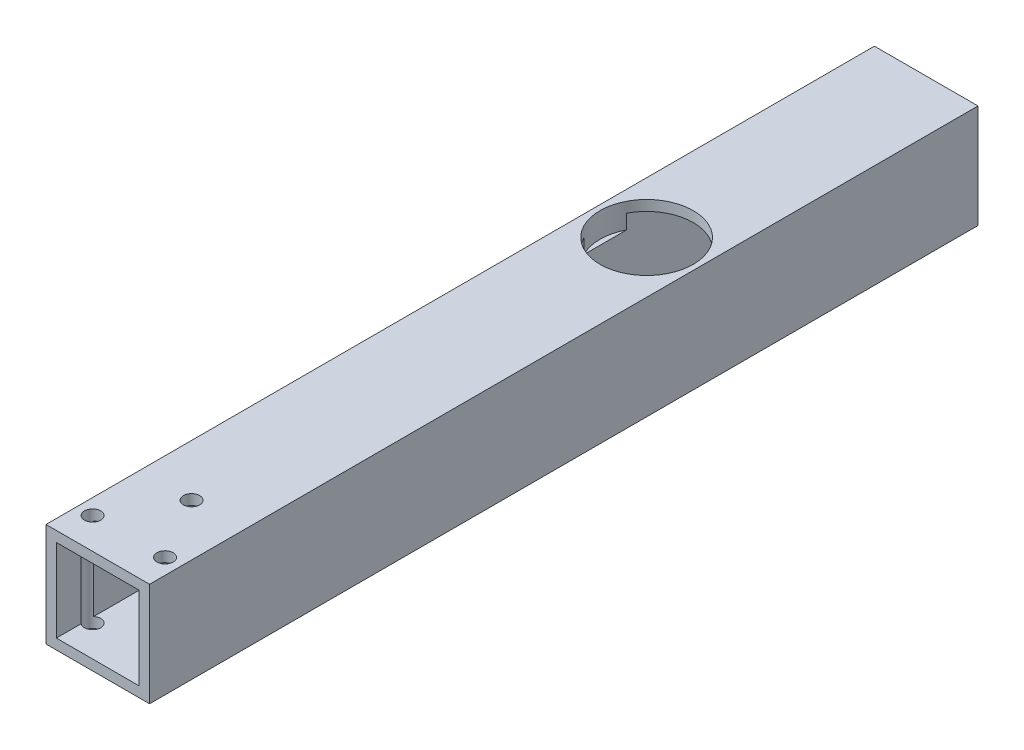
SolidWorks part; units mm, degrees
ref_plane "Front Plane" through (0, 0, 0) normal (0, 0, 1) x (1, 0, 0)
ref_plane "Top Plane" through (0, 0, 0) normal (0, 1, 0) x (1, 0, 0)
ref_plane "Right Plane" through (0, 0, 0) normal (1, 0, 0) x (0, 0, -1)
sketch "Sketch1" plane through (0, 0, 0) normal (0, 0, 1) x (1, 0, 0)
  line L0 (-12.7, 12.7) -> (12.7, 12.7)
  line L2 (-15.875, 15.875) -> (15.875, 15.875)
  line L3 (-15.875, 15.875) -> (-15.875, -15.875)
  line L4 (-15.875, -15.875) -> (15.875, -15.875)
  line L5 (15.875, 15.875) -> (15.875, -15.875)
  line L10 (12.7, 12.7) -> (12.7, -12.7)
  line L11 (-12.7, -12.7) -> (12.7, -12.7)
  line L12 (-12.7, 12.7) -> (-12.7, -12.7)
  point P12 (0, 15.875)
  point P14 (15.875, 0)
  dimension "Wall Thickness" = 3.175
  dimension "Outside Width" = 31.75
  dimension "Outside Height" = 31.75
  dimension "Inside Height" = 25.4
  dimension "Inside Width" = 25.4
sketch "Sketch2" plane through (0, 0, 0) normal (1, 0, 0) x (0, 0, -1)
  line L0 (127, 0) -> (-127, 0)
  point P4 (0, 0)
  point P7 (-127, 0)
  point P10 (127, 0)
  dimension "Length" = 254
sketch "Sketch3" plane through (0, 0, 0) normal (0, 0, 1) x (1, 0, 0)
  line L21 (15.875, 15.875) -> (-15.875, 15.875)
  line L22 (15.875, -15.875) -> (15.875, 15.875)
  line L23 (-15.875, -15.875) -> (15.875, -15.875)
  line L24 (-15.875, 15.875) -> (-15.875, -15.875)
  line L25 (15.875, 15.875) -> (-15.875, 15.875)
  line L26 (15.875, -15.875) -> (15.875, 15.875)
  line L27 (-15.875, -15.875) -> (15.875, -15.875)
  line L28 (-15.875, 15.875) -> (-15.875, -15.875)
  line L29 (12.7, 12.7) -> (-12.7, 12.7)
  line L30 (12.7, -12.7) -> (12.7, 12.7)
  line L31 (-12.7, -12.7) -> (12.7, -12.7)
  line L32 (-12.7, 12.7) -> (-12.7, -12.7)
  line L33 (12.7, 12.7) -> (-12.7, 12.7)
  line L34 (12.7, -12.7) -> (12.7, 12.7)
  line L35 (-12.7, -12.7) -> (12.7, -12.7)
  line L36 (-12.7, 12.7) -> (-12.7, -12.7)
  dimension "D1" = 0
  dimension "D2" = 0
extrude "Boss-Extrude1" add sketch "Sketch3" along normal up to vertex (127 mm away) and the other way up to vertex (127 mm away) up to point (0, 0, 127) other way up to point (0, 0, -127)
sketch "Drawing Reference" plane through (0, 0, 0) normal (1, 0, 0) x (0, 0, -1)
  line L0 (-127, 0) -> (127, 0) construction
  line L1 (0, -15.875) -> (0, 15.875) construction
  line L2 (-127, -15.875) -> (127, -15.875) construction
  line L5 (-127, 15.875) -> (127, 15.875) construction
  point P7 (-104.14, 0)
  point P8 (104.14, 0)
  dimension "D1" = 22.86
sketch "Sketch4" plane through (0, 15.875, 0) normal (0, 1, 0) x (1, 0, 0)
  line L0 (0, -127) -> (0, -117.475) construction
  line L1 (15.875, -127) -> (-15.875, -127) construction
  line L2 (0, -117.475) -> (11.1125, -117.475) construction
  line L3 (0, -117.475) -> (-11.1125, -117.475) construction
  line L4 (0, -117.475) -> (0, 41.275) construction
  line L5 (0, -117.475) -> (0, -98.2472) construction
  dimension "D1" = 158.75
  dimension "D2" = 22.225
hole_wizard "#10 Clearance Hole1" positions "Sketch5" profile "Sketch6" hole size "#10" standard "ANSI Inch" end condition through all
sketch "Sketch5" plane through (0, 15.875, 0) normal (0, 1, 0) x (1, 0, 0)
  point P0 (-11.1125, -117.475)
  point P3 (11.1125, -117.475)
  point P7 (0, -98.2472)
sketch "Sketch6" plane through (-11.1125, 15.875, 117.475) normal (1, 0, 0) x (0, 0, 1)
  line L0 (0, 0) -> (0, 31.75)
  line L1 (0, 31.75) -> (2.4892, 31.75)
  line L2 (2.4892, 31.75) -> (2.4892, 0)
  line L5 (2.4892, 0) -> (0, 0)
  line L11 (0, -6.35) -> (0, 107.95) construction
  dimension "Thru Hole Dia." = 4.9784
  dimension "Thru Hole Depth" = 31.75
sketch "Sketch7" plane through (0, 15.875, 0) normal (0, 1, 0) x (1, 0, 0)
  circle A0 centre (0, 41.275) radius 14.2875
  dimension "D1" = 28.575
extrude "Cut-Extrude1" cut sketch "Sketch7" against normal blind 7.62
sketch "Sketch8" plane through (0, -15.875, 0) normal (0, -1, 0) x (1, 0, 0)
  circle A0 centre (0, -41.275) radius 14.2875
  dimension "D1" = 28.575
extrude "Cut-Extrude2" cut sketch "Sketch8" against normal blind 7.62
equation "\"D1@Drawing Reference\"=\"Outside Width@Sketch1\" * 0.72"
